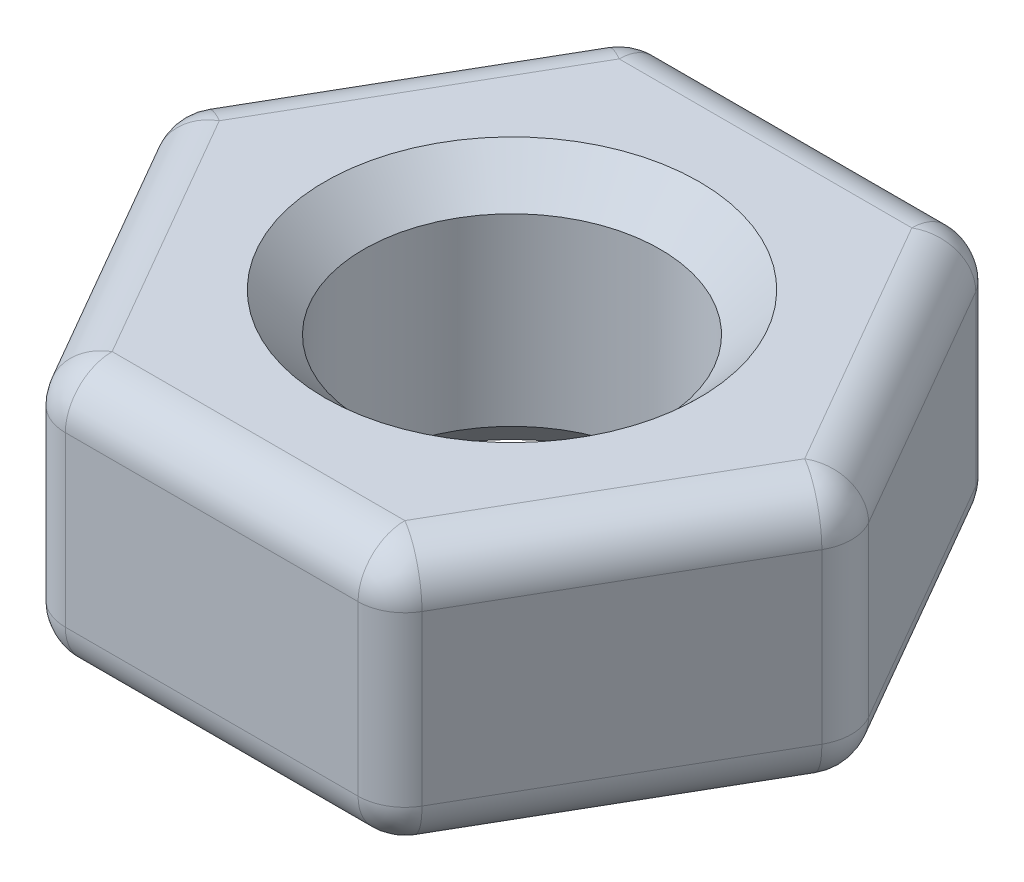
SolidWorks part; units mm, degrees
ref_plane "Front Plane" through (0, 0, 0) normal (0, 0, 1) x (1, 0, 0)
ref_plane "Top Plane" through (0, 0, 0) normal (0, 1, 0) x (1, 0, 0)
ref_plane "Right Plane" through (0, 0, 0) normal (1, 0, 0) x (0, 0, -1)
sketch "Sketch1" plane through (0, 0, 0) normal (0, 1, 0) x (1, 0, 0)
  line L1 (2.2228, 0) -> (1.1114, 1.925)
  line L2 (1.1114, 1.925) -> (-1.1114, 1.925)
  line L3 (-1.1114, 1.925) -> (-2.2228, 0)
  line L4 (-2.2228, 0) -> (-1.1114, -1.925)
  line L5 (-1.1114, -1.925) -> (1.1114, -1.925)
  line L6 (1.1114, -1.925) -> (2.2228, 0)
  circle A0 centre (0, 0) radius 1.925 construction
  circle A1 centre (0, 0) radius 0.95
  dimension "D2" = 1.9
  dimension "D1" = 3.85
extrude "Boss-Extrude1" add sketch "Sketch1" along normal blind 1.68 contours L5 L6 L1 L2 L3 L4 A1 region at (1.6162, 0, 0.9331)
ref_axis "Axis1" through (0, 1.68, 0) along (0, -1, 0)
sketch "Sketch4" plane through (0, 1.68, 0) normal (0, 1, 0) x (1, 0, 0)
  circle A0 centre (0, 0) radius 4
curve "Helix/Spiral1" [suppressed] pitch 1.25 height 5 turns 4
ref_plane "Plane1" [suppressed] through (0, 5, 4) normal (-0.9988, -0.0497, 0) x (0, 0, 1)
chamfer "Chamfer1" [suppressed] distance 0.5 angle 45
sketch "Sketch5" [suppressed] plane through (0, 5, 4) normal (-0.9988, -0.0497, 0) x (0, 0, 1)
  line L0 (0.4983, 0.146) -> (-0.8007, 0.896)
  line L1 (-0.8007, 0.896) -> (-0.8007, -0.604)
  line L2 (-0.8007, -0.604) -> (0.4983, 0.146)
  line L3 (-0.0006, -0.854) -> (0.1004, -0.854) construction
  dimension "D1" = 1.5
ref_axis "Axis2" through (0, 1.68, 0) along (0, -1, 0)
chamfer "Chamfer2" distance 0.25 angle 45 2 edges at (0, 1.68, 0.95) (0, 0, 0.95)
fillet "Fillet1" radius 0.3 18 edges at (1.6671, 1.68, -0.9625) (1.6671, 0, -0.9625) (1.1114, 0.84, -1.925) (0, 1.68, -1.925) (0, 0, -1.925) (-1.1114, 0.84, -1.925) (-1.6671, 1.68, -0.9625) (-1.6671, 0, -0.9625) (-2.2228, 0.84, 0) (-1.6671, 1.68, 0.9625) (-1.6671, 0, 0.9625) (-1.1114, 0.84, 1.925) (0, 1.68, 1.925) (0, 0, 1.925) (1.1114, 0.84, 1.925) (1.6671, 1.68, 0.9625) (2.2228, 0.84, 0) (1.6671, 0, 0.9625)
